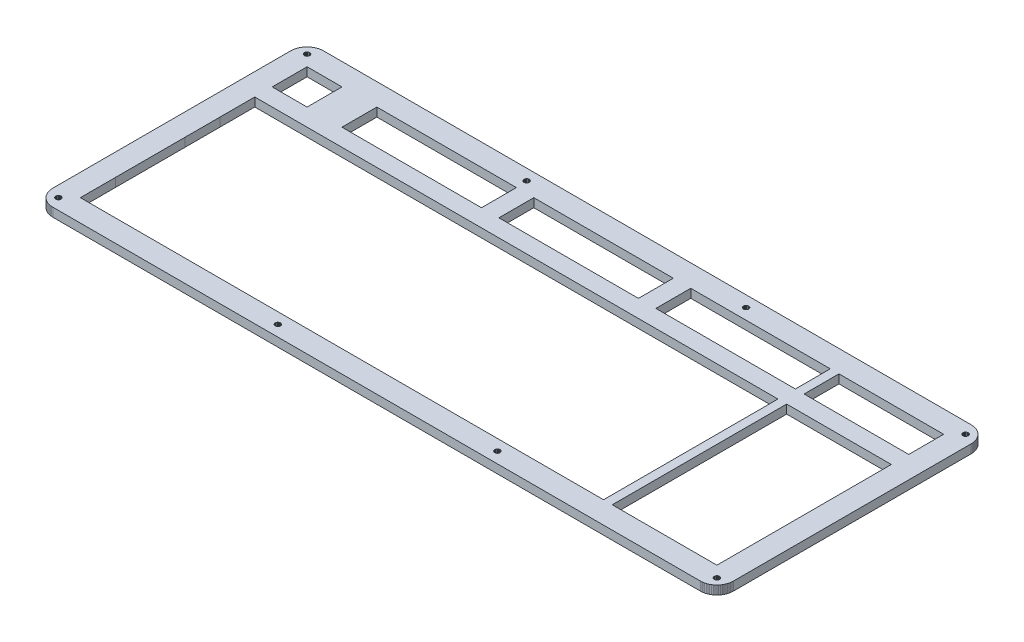
SolidWorks part; units mm, degrees
material "Acrylic (Medium-high impact)"
ref_plane "Front Plane" through (0, 0, 0) normal (0, 0, 1) x (1, 0, 0)
ref_plane "Top Plane" through (0, 0, 0) normal (0, 1, 0) x (1, 0, 0)
ref_plane "Right Plane" through (0, 0, 0) normal (1, 0, 0) x (0, 0, -1)
sketch "Sketch2" plane through (0, 0, 0) normal (0, 1, 0) x (1, 0, 0)
  line L0 (362.807, 147.967) -> (363.513, 147.941)
  line L1 (363.513, 147.941) -> (364.215, 147.857)
  line L2 (364.215, 147.857) -> (364.91, 147.719)
  line L3 (364.91, 147.719) -> (365.591, 147.527)
  line L4 (365.591, 147.527) -> (366.254, 147.282)
  line L5 (366.254, 147.282) -> (366.896, 146.987)
  line L6 (366.896, 146.987) -> (367.51, 146.641)
  line L7 (367.51, 146.641) -> (368.099, 146.25)
  line L8 (368.099, 146.25) -> (368.653, 145.812)
  line L9 (368.653, 145.812) -> (369.171, 145.331)
  line L10 (369.171, 145.331) -> (369.651, 144.812)
  line L11 (369.651, 144.812) -> (370.089, 144.259)
  line L12 (370.089, 144.259) -> (370.48, 143.67)
  line L13 (370.48, 143.67) -> (370.826, 143.053)
  line L14 (370.826, 143.053) -> (371.122, 142.412)
  line L15 (371.122, 142.412) -> (371.369, 141.749)
  line L16 (371.369, 141.749) -> (371.56, 141.07)
  line L17 (371.56, 141.07) -> (371.697, 140.375)
  line L18 (371.697, 140.375) -> (371.778, 139.674)
  line L19 (371.778, 139.674) -> (371.807, 138.967)
  line L20 (371.807, 138.967) -> (371.807, 9.0909)
  line L21 (371.807, 9.0909) -> (371.778, 8.3854)
  line L22 (371.778, 8.3854) -> (371.697, 7.684)
  line L23 (371.697, 7.684) -> (371.56, 6.9908)
  line L24 (371.56, 6.9908) -> (371.369, 6.31)
  line L25 (371.369, 6.31) -> (371.122, 5.6472)
  line L26 (371.122, 5.6472) -> (370.826, 5.0064)
  line L27 (370.826, 5.0064) -> (370.48, 4.3891)
  line L28 (370.48, 4.3891) -> (370.089, 3.8006)
  line L29 (370.089, 3.8006) -> (369.651, 3.2467)
  line L30 (369.651, 3.2467) -> (369.171, 2.7285)
  line L31 (369.171, 2.7285) -> (368.653, 2.2476)
  line L32 (368.653, 2.2476) -> (368.099, 1.8107)
  line L33 (368.099, 1.8107) -> (367.51, 1.418)
  line L34 (367.51, 1.418) -> (366.896, 1.0721)
  line L35 (366.896, 1.0721) -> (366.254, 0.7772)
  line L36 (366.254, 0.7772) -> (365.591, 0.5319)
  line L37 (365.591, 0.5319) -> (364.91, 0.3404)
  line L38 (364.91, 0.3404) -> (364.215, 0.2026)
  line L39 (364.215, 0.2026) -> (363.513, 0.1185)
  line L40 (363.513, 0.1185) -> (362.807, 0.091)
  line L41 (362.807, 0.091) -> (9.0951, 0.091)
  line L42 (9.0951, 0.091) -> (8.3881, 0.1185)
  line L43 (8.3881, 0.1185) -> (7.6867, 0.2026)
  line L44 (7.6867, 0.2026) -> (6.9922, 0.3404)
  line L45 (6.9922, 0.3404) -> (6.3128, 0.5319)
  line L46 (6.3128, 0.5319) -> (5.6499, 0.7772)
  line L47 (5.6499, 0.7772) -> (5.0092, 1.0721)
  line L48 (5.0092, 1.0721) -> (4.3918, 1.418)
  line L49 (4.3918, 1.418) -> (3.8034, 1.8107)
  line L50 (3.8034, 1.8107) -> (3.2494, 2.2476)
  line L51 (3.2494, 2.2476) -> (2.7313, 2.7285)
  line L52 (2.7313, 2.7285) -> (2.2503, 3.2467)
  line L53 (2.2503, 3.2467) -> (1.8121, 3.8006)
  line L54 (1.8121, 3.8006) -> (1.4208, 4.3891)
  line L55 (1.4208, 4.3891) -> (1.0749, 5.0064)
  line L56 (1.0749, 5.0064) -> (0.78, 5.6472)
  line L57 (0.78, 5.6472) -> (0.5347, 6.31)
  line L58 (0.5347, 6.31) -> (0.3431, 6.9908)
  line L59 (0.3431, 6.9908) -> (0.2053, 7.684)
  line L60 (0.2053, 7.684) -> (0.1213, 8.3854)
  line L61 (0.1213, 8.3854) -> (0.0937, 9.0923)
  line L62 (0.0937, 9.0923) -> (0.0951, 138.967)
  line L63 (0.0951, 138.967) -> (0.1213, 139.674)
  line L64 (0.1213, 139.674) -> (0.2053, 140.375)
  line L65 (0.2053, 140.375) -> (0.3431, 141.07)
  line L66 (0.3431, 141.07) -> (0.5347, 141.749)
  line L67 (0.5347, 141.749) -> (0.78, 142.412)
  line L68 (0.78, 142.412) -> (1.0749, 143.053)
  line L69 (1.0749, 143.053) -> (1.4208, 143.67)
  line L70 (1.4208, 143.67) -> (1.8121, 144.259)
  line L71 (1.8121, 144.259) -> (2.2503, 144.812)
  line L72 (2.2503, 144.812) -> (2.7313, 145.331)
  line L73 (2.7313, 145.331) -> (3.2494, 145.812)
  line L74 (3.2494, 145.812) -> (3.8034, 146.25)
  line L75 (3.8034, 146.25) -> (4.3918, 146.641)
  line L76 (4.3918, 146.641) -> (5.0092, 146.987)
  line L77 (5.0092, 146.987) -> (5.6499, 147.282)
  line L78 (5.6499, 147.282) -> (6.3128, 147.527)
  line L79 (6.3128, 147.527) -> (6.9922, 147.719)
  line L80 (6.9922, 147.719) -> (7.6867, 147.857)
  line L81 (7.6867, 147.857) -> (8.3881, 147.941)
  line L82 (8.3881, 147.941) -> (9.0951, 147.968)
  line L83 (9.0951, 147.968) -> (362.807, 147.967)
  line L84 (365.326, 7.5186) -> (364.917, 7.3119)
  line L85 (364.917, 7.3119) -> (364.589, 6.9825)
  line L86 (364.589, 6.9825) -> (364.381, 6.5719)
  line L87 (364.381, 6.5719) -> (364.307, 6.1157)
  line L88 (364.307, 6.1157) -> (364.381, 5.661)
  line L89 (364.381, 5.661) -> (364.589, 5.2503)
  line L90 (364.589, 5.2503) -> (364.917, 4.9237)
  line L91 (364.917, 4.9237) -> (365.326, 4.7143)
  line L92 (365.326, 4.7143) -> (365.781, 4.6413)
  line L93 (365.781, 4.6413) -> (366.24, 4.7143)
  line L94 (366.24, 4.7143) -> (366.649, 4.9237)
  line L95 (366.649, 4.9237) -> (366.977, 5.2503)
  line L96 (366.977, 5.2503) -> (367.185, 5.661)
  line L97 (367.185, 5.661) -> (367.259, 6.1157)
  line L98 (367.259, 6.1157) -> (367.185, 6.5719)
  line L99 (367.185, 6.5719) -> (366.977, 6.9825)
  line L100 (366.977, 6.9825) -> (366.649, 7.3119)
  line L101 (366.649, 7.3119) -> (366.24, 7.5186)
  line L102 (366.24, 7.5186) -> (365.781, 7.5916)
  line L103 (365.781, 7.5916) -> (365.326, 7.5186)
  line L104 (245.438, 7.5186) -> (245.027, 7.3119)
  line L105 (245.027, 7.3119) -> (244.703, 6.9825)
  line L106 (244.703, 6.9825) -> (244.492, 6.5719)
  line L107 (244.492, 6.5719) -> (244.42, 6.1157)
  line L108 (244.42, 6.1157) -> (244.492, 5.661)
  line L109 (244.492, 5.661) -> (244.703, 5.2503)
  line L110 (244.703, 5.2503) -> (245.027, 4.9237)
  line L111 (245.027, 4.9237) -> (245.438, 4.7143)
  line L112 (245.438, 4.7143) -> (245.894, 4.6413)
  line L113 (245.894, 4.6413) -> (246.35, 4.7143)
  line L114 (246.35, 4.7143) -> (246.761, 4.9237)
  line L115 (246.761, 4.9237) -> (247.088, 5.2503)
  line L116 (247.088, 5.2503) -> (247.297, 5.661)
  line L117 (247.297, 5.661) -> (247.37, 6.1157)
  line L118 (247.37, 6.1157) -> (247.297, 6.5719)
  line L119 (247.297, 6.5719) -> (247.088, 6.9825)
  line L120 (247.088, 6.9825) -> (246.761, 7.3119)
  line L121 (246.761, 7.3119) -> (246.35, 7.5186)
  line L122 (246.35, 7.5186) -> (245.894, 7.5916)
  line L123 (245.894, 7.5916) -> (245.438, 7.5186)
  line L124 (125.552, 7.5186) -> (125.138, 7.3119)
  line L125 (125.138, 7.3119) -> (124.815, 6.9825)
  line L126 (124.815, 6.9825) -> (124.604, 6.5719)
  line L127 (124.604, 6.5719) -> (124.532, 6.1157)
  line L128 (124.532, 6.1157) -> (124.604, 5.661)
  line L129 (124.604, 5.661) -> (124.815, 5.2503)
  line L130 (124.815, 5.2503) -> (125.138, 4.9237)
  line L131 (125.138, 4.9237) -> (125.552, 4.7143)
  line L132 (125.552, 4.7143) -> (126.007, 4.6413)
  line L133 (126.007, 4.6413) -> (126.463, 4.7143)
  line L134 (126.463, 4.7143) -> (126.873, 4.9237)
  line L135 (126.873, 4.9237) -> (127.201, 5.2503)
  line L136 (127.201, 5.2503) -> (127.409, 5.661)
  line L137 (127.409, 5.661) -> (127.482, 6.1157)
  line L138 (127.482, 6.1157) -> (127.409, 6.5719)
  line L139 (127.409, 6.5719) -> (127.201, 6.9825)
  line L140 (127.201, 6.9825) -> (126.873, 7.3119)
  line L141 (126.873, 7.3119) -> (126.463, 7.5186)
  line L142 (126.463, 7.5186) -> (126.007, 7.5916)
  line L143 (126.007, 7.5916) -> (125.552, 7.5186)
  line L144 (5.6637, 7.5186) -> (5.2531, 7.3119)
  line L145 (5.2531, 7.3119) -> (4.9251, 6.9825)
  line L146 (4.9251, 6.9825) -> (4.717, 6.5719)
  line L147 (4.717, 6.5719) -> (4.644, 6.1157)
  line L148 (4.644, 6.1157) -> (4.717, 5.661)
  line L149 (4.717, 5.661) -> (4.9251, 5.2503)
  line L150 (4.9251, 5.2503) -> (5.2531, 4.9237)
  line L151 (5.2531, 4.9237) -> (5.6637, 4.7143)
  line L152 (5.6637, 4.7143) -> (6.1185, 4.6413)
  line L153 (6.1185, 4.6413) -> (6.5746, 4.7143)
  line L154 (6.5746, 4.7143) -> (6.9853, 4.9237)
  line L155 (6.9853, 4.9237) -> (7.3133, 5.2503)
  line L156 (7.3133, 5.2503) -> (7.5213, 5.661)
  line L157 (7.5213, 5.661) -> (7.5944, 6.1157)
  line L158 (7.5944, 6.1157) -> (7.5213, 6.5719)
  line L159 (7.5213, 6.5719) -> (7.3133, 6.9825)
  line L160 (7.3133, 6.9825) -> (6.9853, 7.3119)
  line L161 (6.9853, 7.3119) -> (6.5746, 7.5186)
  line L162 (6.5746, 7.5186) -> (6.1185, 7.5916)
  line L163 (6.1185, 7.5916) -> (5.6637, 7.5186)
  line L164 (12.1171, 107.369) -> (12.1171, 88.3186)
  line L165 (12.1171, 88.3186) -> (12.1185, 88.3186)
  line L166 (12.1185, 88.3186) -> (12.1185, 69.2686)
  line L167 (12.1185, 69.2686) -> (12.1171, 69.2686)
  line L168 (12.1171, 69.2686) -> (12.1171, 31.1685)
  line L169 (12.1171, 31.1685) -> (12.1185, 31.1685)
  line L170 (12.1185, 31.1685) -> (12.1185, 12.1157)
  line L171 (12.1185, 12.1157) -> (297.87, 12.1157)
  line L172 (297.87, 12.1157) -> (297.87, 31.1685)
  line L173 (297.87, 31.1685) -> (297.871, 31.1685)
  line L174 (297.871, 31.1685) -> (297.871, 107.369)
  line L175 (297.871, 107.369) -> (12.1171, 107.369)
  line L176 (302.631, 107.369) -> (359.784, 107.369)
  line L177 (359.784, 107.369) -> (359.784, 12.1157)
  line L178 (359.784, 12.1157) -> (302.631, 12.1157)
  line L179 (302.631, 12.1157) -> (302.631, 107.369)
  line L180 (12.1171, 135.945) -> (31.1699, 135.945)
  line L181 (31.1699, 135.945) -> (31.1699, 116.892)
  line L182 (31.1699, 116.892) -> (12.1171, 116.892)
  line L183 (12.1171, 116.892) -> (12.1171, 135.945)
  line L184 (50.2186, 135.945) -> (126.421, 135.945)
  line L185 (126.421, 135.945) -> (126.421, 116.892)
  line L186 (126.421, 116.892) -> (50.2186, 116.892)
  line L187 (50.2186, 116.892) -> (50.2186, 135.945)
  line L188 (135.944, 135.945) -> (212.146, 135.945)
  line L189 (212.146, 135.945) -> (212.146, 116.892)
  line L190 (212.146, 116.892) -> (135.944, 116.892)
  line L191 (135.944, 116.892) -> (135.944, 135.945)
  line L192 (221.669, 135.945) -> (297.871, 135.945)
  line L193 (297.871, 135.945) -> (297.871, 116.892)
  line L194 (297.871, 116.892) -> (221.669, 116.892)
  line L195 (221.669, 116.892) -> (221.669, 135.945)
  line L196 (302.631, 135.945) -> (359.784, 135.945)
  line L197 (359.784, 135.945) -> (359.784, 116.892)
  line L198 (359.784, 116.892) -> (302.631, 116.892)
  line L199 (302.631, 116.892) -> (302.631, 135.945)
  line L200 (125.552, 143.345) -> (125.138, 143.137)
  line L201 (125.138, 143.137) -> (124.815, 142.809)
  line L202 (124.815, 142.809) -> (124.604, 142.398)
  line L203 (124.604, 142.398) -> (124.532, 141.942)
  line L204 (124.532, 141.942) -> (124.604, 141.487)
  line L205 (124.604, 141.487) -> (124.815, 141.077)
  line L206 (124.815, 141.077) -> (125.138, 140.75)
  line L207 (125.138, 140.75) -> (125.552, 140.541)
  line L208 (125.552, 140.541) -> (126.007, 140.468)
  line L209 (126.007, 140.468) -> (126.463, 140.541)
  line L210 (126.463, 140.541) -> (126.873, 140.75)
  line L211 (126.873, 140.75) -> (127.201, 141.077)
  line L212 (127.201, 141.077) -> (127.409, 141.487)
  line L213 (127.409, 141.487) -> (127.482, 141.942)
  line L214 (127.482, 141.942) -> (127.409, 142.398)
  line L215 (127.409, 142.398) -> (127.201, 142.809)
  line L216 (127.201, 142.809) -> (126.873, 143.137)
  line L217 (126.873, 143.137) -> (126.463, 143.345)
  line L218 (126.463, 143.345) -> (126.007, 143.417)
  line L219 (126.007, 143.417) -> (125.552, 143.345)
  line L220 (245.438, 143.345) -> (245.027, 143.137)
  line L221 (245.027, 143.137) -> (244.703, 142.809)
  line L222 (244.703, 142.809) -> (244.492, 142.398)
  line L223 (244.492, 142.398) -> (244.42, 141.942)
  line L224 (244.42, 141.942) -> (244.492, 141.487)
  line L225 (244.492, 141.487) -> (244.703, 141.077)
  line L226 (244.703, 141.077) -> (245.027, 140.75)
  line L227 (245.027, 140.75) -> (245.438, 140.541)
  line L228 (245.438, 140.541) -> (245.894, 140.468)
  line L229 (245.894, 140.468) -> (246.35, 140.541)
  line L230 (246.35, 140.541) -> (246.761, 140.75)
  line L231 (246.761, 140.75) -> (247.088, 141.077)
  line L232 (247.088, 141.077) -> (247.297, 141.487)
  line L233 (247.297, 141.487) -> (247.37, 141.942)
  line L234 (247.37, 141.942) -> (247.297, 142.398)
  line L235 (247.297, 142.398) -> (247.088, 142.809)
  line L236 (247.088, 142.809) -> (246.761, 143.137)
  line L237 (246.761, 143.137) -> (246.35, 143.345)
  line L238 (246.35, 143.345) -> (245.894, 143.417)
  line L239 (245.894, 143.417) -> (245.438, 143.345)
  line L240 (365.326, 143.345) -> (364.917, 143.137)
  line L241 (364.917, 143.137) -> (364.589, 142.809)
  line L242 (364.589, 142.809) -> (364.381, 142.398)
  line L243 (364.381, 142.398) -> (364.307, 141.942)
  line L244 (364.307, 141.942) -> (364.381, 141.487)
  line L245 (364.381, 141.487) -> (364.589, 141.077)
  line L246 (364.589, 141.077) -> (364.917, 140.75)
  line L247 (364.917, 140.75) -> (365.326, 140.541)
  line L248 (365.326, 140.541) -> (365.781, 140.468)
  line L249 (365.781, 140.468) -> (366.24, 140.541)
  line L250 (366.24, 140.541) -> (366.649, 140.75)
  line L251 (366.649, 140.75) -> (366.977, 141.077)
  line L252 (366.977, 141.077) -> (367.185, 141.487)
  line L253 (367.185, 141.487) -> (367.259, 141.942)
  line L254 (367.259, 141.942) -> (367.185, 142.398)
  line L255 (367.185, 142.398) -> (366.977, 142.809)
  line L256 (366.977, 142.809) -> (366.649, 143.137)
  line L257 (366.649, 143.137) -> (366.24, 143.345)
  line L258 (366.24, 143.345) -> (365.781, 143.417)
  line L259 (365.781, 143.417) -> (365.326, 143.345)
  line L260 (5.6637, 143.345) -> (5.2531, 143.137)
  line L261 (5.2531, 143.137) -> (4.9251, 142.809)
  line L262 (4.9251, 142.809) -> (4.717, 142.398)
  line L263 (4.717, 142.398) -> (4.644, 141.942)
  line L264 (4.644, 141.942) -> (4.717, 141.487)
  line L265 (4.717, 141.487) -> (4.9251, 141.077)
  line L266 (4.9251, 141.077) -> (5.2531, 140.75)
  line L267 (5.2531, 140.75) -> (5.6637, 140.541)
  line L268 (5.6637, 140.541) -> (6.1185, 140.468)
  line L269 (6.1185, 140.468) -> (6.5746, 140.541)
  line L270 (6.5746, 140.541) -> (6.9853, 140.75)
  line L271 (6.9853, 140.75) -> (7.3133, 141.077)
  line L272 (7.3133, 141.077) -> (7.5213, 141.487)
  line L273 (7.5213, 141.487) -> (7.5944, 141.942)
  line L274 (7.5944, 141.942) -> (7.5213, 142.398)
  line L275 (7.5213, 142.398) -> (7.3133, 142.809)
  line L276 (7.3133, 142.809) -> (6.9853, 143.137)
  line L277 (6.9853, 143.137) -> (6.5746, 143.345)
  line L278 (6.5746, 143.345) -> (6.1185, 143.417)
  line L279 (6.1185, 143.417) -> (5.6637, 143.345)
extrude "Boss-Extrude1" add sketch "Sketch2" along normal blind 4.7625
